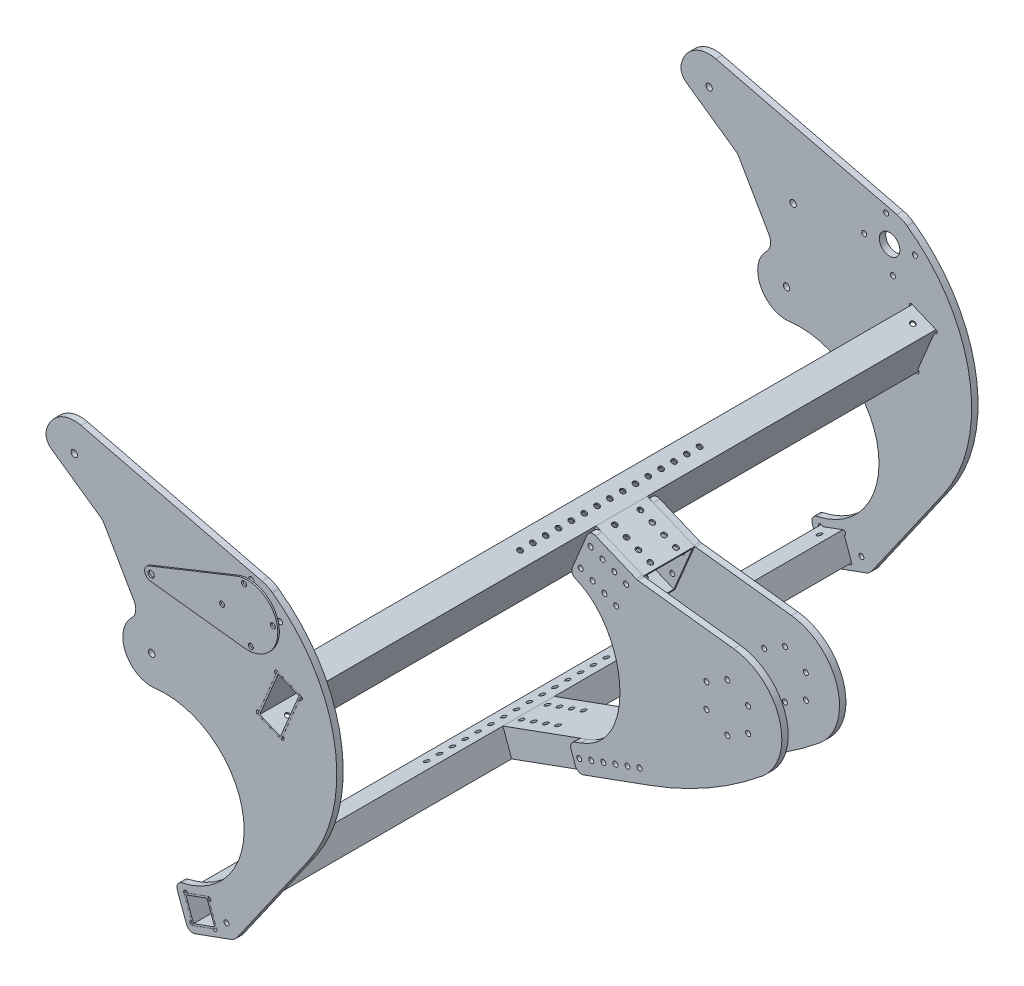
SolidWorks part; units mm, degrees
ref_plane "Front Plane" through (0, 0, 0) normal (0, 0, 1) x (1, 0, 0)
ref_plane "Top Plane" through (0, 0, 0) normal (0, 1, 0) x (1, 0, 0)
ref_plane "Right Plane" through (0, 0, 0) normal (1, 0, 0) x (0, 0, -1)
sketch "citrus are on lsd" plane through (0, 0, 0) normal (0, 0, 1) x (1, 0, 0)
  line L0 (-284.2463, 47.3015) -> (-284.2463, 72.7015) construction
  line L1 (-284.2463, 47.3015) -> (-277.7091, 122.0222) construction
  line L2 (-360.9349, 180.2976) -> (-277.7091, 122.0222) construction
  line L3 (-284.2463, 47.3015) -> (-309.6463, 47.3015) construction
  line L4 (-252.4225, -141.9521) -> (-228.5543, -133.2647)
  line L5 (0, 0) -> (50.8, 0) construction
  line L6 (-252.4225, -141.9521) -> (-243.7352, -165.8203)
  line L7 (-243.7352, -165.8203) -> (-219.867, -157.1329)
  line L8 (-219.867, -157.1329) -> (-228.5543, -133.2647)
  line L9 (-179.3681, 47.4325) -> (-155.9323, 37.6382)
  line L10 (-179.3681, 47.4325) -> (-159.7796, 94.3039)
  line L11 (-155.9323, 37.6382) -> (-136.3439, 84.5097)
  line L12 (-159.7796, 94.3039) -> (-136.3439, 84.5097)
  line L13 (-169.5738, 70.8682) -> (0, 0) construction
  line L14 (-136.3439, 84.5097) -> (-155.9323, 37.6382)
  line L15 (-136.3439, 84.5097) -> (-89.4724, 64.9212)
  line L16 (-155.9323, 37.6382) -> (-109.0609, 18.0498)
  line L17 (-89.4724, 64.9212) -> (-109.0609, 18.0498)
  line L18 (-228.5543, -133.2647) -> (-219.867, -157.1329)
  line L19 (-228.5543, -133.2647) -> (-85.3451, -81.1409)
  line L20 (-219.867, -157.1329) -> (-76.6578, -105.0091)
  line L21 (-85.3451, -81.1409) -> (-76.6578, -105.0091)
  circle A0 centre (0, 0) radius 50.3428 construction
  circle A2 centre (-284.2463, 47.3015) radius 25.4
  circle A3 centre (-277.7091, 122.0222) radius 25.4
  circle A4 centre (-360.9349, 180.2976) radius 25.4
  circle A5 centre (-236.1447, -149.5425) radius 12.7
  circle A6 centre (-182.2333, 134.7222) radius 30
  circle A7 centre (-182.2333, 134.7222) radius 11.5 construction
  circle A8 centre (-277.7091, 122.0222) radius 25.5 construction
  dimension "D4" = 50.8
  dimension "D3" = 75.0062
  dimension "D5" = 5
  dimension "D6" = 35
  dimension "D7" = 101.6
  dimension "D8" = 20
  dimension "D9" = 188.7245
  dimension "D10" = 25.4
  dimension "D11" = 260.35
  dimension "D12" = 149.5425
  dimension "D14" = 50.8
  dimension "D15" = 25.4
  dimension "D16" = 183.7868
  dimension "D17" = 22.681
  dimension "D19" = 96.3168
  dimension "D22" = 12.7
  dimension "D13" = 284.2463
  dimension "D23" = 152.4
  dimension "D24" = 50.8
sketch "rudimentary topdown" plane through (0, 0, 0) normal (0, 1, 0) x (1, 0, 0)
  line L0 (0, 330.2) -> (0, -330.2) construction
  line L1 (0, -31.75) -> (-179.3681, -31.75) construction
  line L2 (0, 25.4) -> (-179.3681, 25.4)
  line L3 (0, 25.4) -> (0, -25.4)
  line L4 (0, -25.4) -> (-179.3681, -25.4)
  line L5 (-179.3681, 25.4) -> (-179.3681, -25.4)
  line L6 (0, 0) -> (-481.5631, 0) construction
  line L7 (0, -317.5) -> (-386.3349, -317.5) construction
  line L8 (0, 31.75) -> (-179.3681, 31.75) construction
  line L9 (0, 311.15) -> (-386.3349, 311.15) construction
  line L10 (0, -311.15) -> (-386.3349, -311.15) construction
  line L11 (0, 317.5) -> (-386.3349, 317.5) construction
  line L12 (-360.9349, 317.5) -> (-360.9349, -317.5) construction
  line L13 (-277.7091, 317.5) -> (-277.7091, -317.5) construction
  line L14 (-284.2463, 317.5) -> (-284.2463, -317.5) construction
  line L15 (-179.3681, 317.5) -> (-179.3681, -317.5)
  line L16 (-386.3349, 317.5) -> (-335.5349, 317.5)
  line L17 (-386.3349, 317.5) -> (-386.3349, -317.5)
  line L18 (-386.3349, -317.5) -> (-335.5349, -317.5)
  line L19 (-335.5349, 317.5) -> (-335.5349, -317.5)
  line L20 (-309.6463, 317.5) -> (-252.3091, 317.5)
  line L21 (-309.6463, 317.5) -> (-309.6463, -317.5)
  line L22 (-309.6463, -317.5) -> (-252.3091, -317.5)
  line L23 (-252.3091, 317.5) -> (-252.3091, -317.5)
  line L24 (-136.3439, -317.5) -> (-136.3439, 317.5)
  line L25 (0, -330.2) -> (-386.3349, -330.2)
  line L26 (-252.4225, 317.5) -> (-219.867, 317.5)
  line L27 (-252.4225, 317.5) -> (-252.4225, -317.5)
  line L28 (-252.4225, -317.5) -> (-219.867, -317.5)
  line L29 (-219.867, 317.5) -> (-219.867, -317.5)
  line L31 (0, 330.2) -> (-386.3349, 330.2)
  point P4 (0, 0)
  point P11 (0, 0)
  dimension "D1" = 660.4
  dimension "D2" = 50.8
  dimension "D4" = 6.35
  dimension "D5" = 6.35
  dimension "D6" = 311.15
  dimension "D8" = 50.8
  dimension "D9" = 25.4
  dimension "D10" = 25.4
  dimension "D11" = 25.4
ref_plane "attachplateplane" through (0, 0, 25.4) normal (0, 0, 1) x (1, 0, 0)
ref_plane "intakeplateplane" through (0, 0, 311.15) normal (0, 0, 1) x (1, 0, 0)
sketch "intakeplate" plane through (0, 0, 311.15) normal (0, 0, 1) x (1, 0, 0)
  line L0 (-354.2108, 207.7434) -> (-175.0945, 163.8605)
  line L1 (-199.728, -154.1663) -> (-128.4497, -52.2564)
  line L3 (-360.9349, 180.2976) -> (-236.1447, -149.5425) construction
  line L4 (-255.0764, -134.809) -> (-243.3357, -130.5357) construction
  line L5 (-252.4225, -141.9521) -> (-228.5543, -133.2647) construction
  line L6 (-383.4957, 172.839) -> (-334.9996, 138.8818)
  line L7 (-331.2821, 134.8225) -> (-301.7087, 83.5353)
  line L8 (-137.8969, 80.6618) -> (-136.2774, 84.537) construction
  line L15 (-241.5937, -171.8524) -> (-205.7914, -158.8214)
  line L16 (-258.8716, -142.9479) -> (-249.7326, -168.0572)
  line L17 (-159.8069, 94.3704) -> (-161.4264, 90.4952) construction
  line L18 (-360.9349, 180.2976) -> (-277.7091, 122.0222) construction
  line L19 (-360.9349, 180.2976) -> (-284.2463, 47.3015) construction
  line L30 (-185.5824, 159.9005) -> (-182.2333, 134.7222) construction
  line L31 (-277.7091, 122.0222) -> (-182.2333, 134.7222) construction
  line L40 (-136.2774, 84.537) -> (-159.8069, 94.3704)
  line L41 (-159.8069, 94.3704) -> (-179.4345, 47.4052)
  line L42 (-179.4345, 47.4052) -> (-155.9051, 37.5718)
  line L43 (-155.9051, 37.5718) -> (-136.2774, 84.537)
  line L44 (-136.2774, 84.537) -> (-159.8069, 94.3704)
  line L45 (-161.4264, 90.4952) -> (-177.815, 51.2804)
  line L46 (-179.4345, 47.4052) -> (-155.9051, 37.5718)
  line L47 (-154.2855, 41.447) -> (-137.8969, 80.6618)
  line L48 (-227.0874, -137.1463) -> (-228.5239, -133.1996) construction
  line L49 (-223.7486, -158.5998) -> (-219.8019, -157.1633) construction
  line L50 (-245.202, -161.9387) -> (-243.7655, -165.8854) construction
  line L51 (-248.5409, -140.4852) -> (-252.4876, -141.9217) construction
  line L52 (-252.4876, -141.9217) -> (-243.7655, -165.8854)
  line L53 (-243.7655, -165.8854) -> (-219.8019, -157.1633)
  line L54 (-228.5239, -133.1996) -> (-252.4876, -141.9217)
  line L55 (-219.8019, -157.1633) -> (-228.5239, -133.1996)
  line L56 (-252.4876, -141.9217) -> (-245.202, -161.9387)
  line L57 (-243.7655, -165.8854) -> (-223.7486, -158.5998)
  line L58 (-228.5239, -133.1996) -> (-248.5409, -140.4852)
  line L59 (-219.8019, -157.1633) -> (-227.0874, -137.1463)
  line L60 (-155.9323, 37.6382) -> (-136.3439, 84.5097) construction
  line L61 (-155.9051, 37.5718) -> (-154.2855, 41.447) construction
  line L62 (-177.815, 51.2804) -> (-179.4345, 47.4052) construction
  arc A0 (-354.2108, 207.7434) -> (-388.6817, 185.6461) centre (-360.9349, 180.2976) ccw
  arc A2 (-303.9524, 67.9945) -> (-280.5976, 18.9604) centre (-284.2463, 47.3015) ccw
  circle A3 centre (-284.2463, 47.3015) radius 3.1877
  circle A4 centre (-277.7091, 122.0222) radius 3.1877
  circle A5 centre (-360.9349, 180.2976) radius 3.1877
  arc A6 (-241.5937, -171.8524) -> (-249.7326, -168.0572) centre (-243.7655, -165.8854) cw
  arc A9 (-164.8065, 159.1417) -> (-175.0945, 163.8605) centre (-182.2333, 134.7222) ccw
  arc A10 (-164.8065, 159.1417) -> (-128.4497, -52.2564) centre (-253.3344, 35.091) cw
  circle A11 centre (-182.2333, 134.7222) radius 30 construction
  arc A12 (-199.728, -154.1663) -> (-205.7914, -158.8214) centre (-210.1351, -146.8873) cw
  arc A14 (-254.2407, -134.5682) -> (-258.8716, -142.9479) centre (-252.9046, -140.776) ccw
  arc A15 (-284.2463, 47.3015) -> (-236.1447, -149.5425) centre (-272.2654, -54.07) cw construction
  arc A18 (-301.7087, 83.5353) -> (-303.9524, 67.9945) centre (-312.7107, 77.1913) cw
  arc A19 (-334.9996, 138.8818) -> (-331.2821, 134.8225) centre (-342.2841, 128.4785) cw
  arc A20 (-383.4957, 172.839) -> (-388.6817, 185.6461) centre (-376.2112, 183.2423) cw
  arc A21 (-280.5976, 18.9604) -> (-254.2407, -134.5682) centre (-270.6433, -58.3574) cw
  circle A25 centre (-182.2333, 134.7222) radius 25.4 construction
  circle A26 centre (-185.5824, 159.9005) radius 2.4892
  circle A27 centre (-157.055, 138.0714) radius 2.4892
  circle A28 centre (-178.8841, 109.544) radius 2.4892
  circle A29 centre (-207.4115, 131.3731) radius 2.4892
  arc A30 (-228.5239, -133.1996) -> (-227.0874, -137.1463) centre (-227.8057, -135.173) cw
  arc A31 (-219.8019, -157.1633) -> (-223.7486, -158.5998) centre (-221.7752, -157.8815) cw
  arc A32 (-243.7655, -165.8854) -> (-245.202, -161.9387) centre (-244.4838, -163.912) cw
  arc A33 (-252.4876, -141.9217) -> (-248.5409, -140.4852) centre (-250.5142, -141.2035) cw
  arc A34 (-155.9051, 37.5718) -> (-154.2855, 41.447) centre (-155.0953, 39.5094) ccw
  arc A35 (-159.8069, 94.3704) -> (-161.4264, 90.4952) centre (-160.6166, 92.4328) ccw
  arc A36 (-136.2774, 84.537) -> (-137.9436, 80.6819) centre (-137.0872, 82.5994) cw
  arc A37 (-179.4345, 47.4052) -> (-177.815, 51.2804) centre (-178.6248, 49.3428) cw
  circle A38 centre (-182.2333, 134.7222) radius 10.16
  circle A39 centre (-210.1351, -146.8873) radius 2.4892
  point P64 (-182.2333, 134.7222)
  point P83 (-236.1447, -149.5425)
  dimension "D2" = 6.35
  dimension "D4" = 152.4
  dimension "D5" = 6.3754
  dimension "D6" = 56.515
  dimension "D7" = 57.15
  dimension "D8" = 102.077
  dimension "D13" = 12.7
  dimension "D11" = 50.8
  dimension "D15" = 4.9784
  dimension "D18" = 2.1
  dimension "D20" = 2.1
  dimension "D23" = 20.32
  dimension "D24" = 4.9784
  dimension "D3" = 127
  dimension "D9" = 7.62
  dimension "D10" = 38.1
  dimension "D12" = 19.05
  dimension "D21" = 6.35
  dimension "D22" = 6.35
  dimension "D14" = 4
sketch "attachplate" plane through (0, 0, 25.4) normal (0, 0, 1) x (1, 0, 0)
  line L0 (-136.3439, 84.5097) -> (-155.9323, 37.6382)
  line L1 (-136.3439, 84.5097) -> (-89.4724, 64.9212)
  line L2 (-155.9323, 37.6382) -> (-109.0609, 18.0498)
  line L3 (-89.4724, 64.9212) -> (-109.0609, 18.0498) construction
  line L4 (-228.5543, -133.2647) -> (-219.867, -157.1329) construction
  line L5 (-156.9497, -107.2028) -> (-85.3451, -81.1409)
  line L6 (-148.2624, -131.071) -> (-76.6578, -105.0091)
  line L7 (-85.3451, -81.1409) -> (-76.6578, -105.0091) construction
  line L8 (-81.0015, -93.075) -> (-152.606, -119.1369) construction
  line L9 (6.3329, 53.6022) -> (-89.4724, 64.9212)
  line L10 (-156.9497, -107.2028) -> (-148.2624, -131.071)
  line L11 (-219.867, -157.1329) -> (-148.2624, -131.071) construction
  line L12 (-228.5543, -133.2647) -> (-156.9497, -107.2028) construction
  line L14 (-169.5738, 70.8682) -> (0, 0) construction
  line L15 (-169.5738, 70.8682) -> (0, 0) construction
  line L16 (-85.3451, -81.1409) -> (-123.6697, 24.1551) construction
  arc A0 (34.2825, -41.6895) -> (6.3329, 53.6022) centre (0, 0) ccw
  circle A1 centre (0, 23.8125) radius 2.4892
  circle A2 centre (20.6222, 11.9063) radius 2.4892
  circle A3 centre (20.6222, -11.9062) radius 2.4892
  circle A4 centre (0, -23.8125) radius 2.4892
  circle A5 centre (-20.6222, -11.9063) radius 2.4892
  circle A6 centre (-20.6222, 11.9062) radius 2.4892
  circle A7 centre (0, 0) radius 23.8125 construction
  arc A9 (-76.6578, -105.0091) -> (34.2825, -41.6895) centre (-206.0995, 250.6289) ccw
  circle A10 centre (-100.2285, 55.6519) radius 2.4892
  circle A11 centre (-111.9463, 60.549) radius 2.4892
  arc A12 (6.3329, 53.6022) -> (34.2825, -41.6895) centre (0, 0) ccw construction
  circle A13 centre (-86.9685, -95.2468) radius 2.4892
  circle A14 centre (-98.9026, -99.5905) radius 2.4892
  circle A15 centre (-110.8367, -103.9341) radius 2.4892
  circle A16 centre (-122.7708, -108.2778) radius 2.4892
  circle A17 centre (-134.7049, -112.6214) radius 2.4892
  circle A18 centre (-123.6642, 65.4461) radius 2.4892
  circle A19 centre (-135.382, 70.3433) radius 2.4892
  circle A20 centre (-146.639, -116.9651) radius 2.4892
  circle A21 centre (-145.1763, 46.9075) radius 2.4892
  circle A22 centre (-133.4584, 42.0104) radius 2.4892
  circle A23 centre (-121.7406, 37.1133) radius 2.4892
  circle A24 centre (-110.0227, 32.2162) radius 2.4892
  spline S0 degree 3 poles (-145.0156, -102.8592) (-86.7961, -81.669) (-99.0931, 15.0965) (-150.0777, 35.1793) knots 0 0 0 0 1 1 1 1
  point P29 (0, 0)
  dimension "D1" = 107.95
  dimension "D4" = 4.9784
  dimension "D6" = 47.625
  dimension "D10" = 4.9784
  dimension "D18" = 4.9784
  dimension "D2" = 50.8
  dimension "D3" = 152.4
  dimension "D7" = 76.2
  dimension "D9" = 6.35
  dimension "D11" = 12.7
  dimension "D12" = 12.7
  dimension "D13" = 6.35
  dimension "D14" = 109.4363
  dimension "D15" = 138.1559
  dimension "D16" = 12.7
  dimension "D17" = 6.35
  dimension "D20" = 12.7
  dimension "D8" = 6
  dimension "D19" = 4
  dimension "D5" = 6
ref_plane "motorstiffplane" through (0, 0, 323.85) normal (0, 0, 1) x (1, 0, 0)
sketch "motorplate" plane through (0, 0, 323.85) normal (0, 0, 1) x (1, 0, 0)
  line L0 (-280.0663, 127.9185) -> (-193.3699, 162.5786)
  line L1 (-185.7007, 104.9233) -> (-278.443, 115.7148)
  circle A0 centre (-277.7091, 122.0222) radius 3.1877 construction
  circle A1 centre (-207.4115, 131.3731) radius 2.4892 construction
  circle A2 centre (-178.8841, 109.544) radius 2.4892 construction
  circle A3 centre (-157.055, 138.0714) radius 2.4892 construction
  circle A4 centre (-185.5824, 159.9005) radius 2.4892 construction
  circle A5 centre (-277.7091, 122.0222) radius 3.1877
  circle A6 centre (-207.4115, 131.3731) radius 2.4892
  circle A7 centre (-178.8841, 109.544) radius 2.4892
  circle A8 centre (-157.055, 138.0714) radius 2.4892
  circle A9 centre (-185.5824, 159.9005) radius 2.4892
  arc A10 (-185.7007, 104.9233) -> (-193.3699, 162.5786) centre (-182.2333, 134.7222) ccw
  arc A11 (-280.0663, 127.9185) -> (-278.443, 115.7148) centre (-277.7091, 122.0222) ccw
  arc A12 (-278.443, 115.7148) -> (-280.0663, 127.9185) centre (-277.7091, 122.0222) ccw construction
  arc A13 (-193.3699, 162.5786) -> (-185.7007, 104.9233) centre (-182.2333, 134.7222) ccw construction
  circle A14 centre (-182.2333, 134.7222) radius 30 construction
  dimension "D1" = 6.35
extrude "intake plate" add sketch "intakeplate" along normal blind 6.35 contours A2 A21 A14 L16 A6 L15 A12 L1 A10 A9 L0 A0 A20 L6 A19 L7 A18 A38 A29 A28 A27 A26 A3 A4 A5 L56 A33 L58 A30 L59 A31 L57 A32 L46 A37 L45 A35 L44 A36 L47 A34 region at (-219.5502, 62.0927, 311.15)
extrude "attach plate" add sketch "attachplate" along normal blind 6.35 separate body contours S0 L5 L10 L6 A9 A0 L9 L1 L0 L2 A23 A21 A20 A19 A18 A17 A16 A15 A14 A13 A11 A10 A6 A5 A4 A3 A2 A1 region at (-53.0442, -13.4193, 25.4)
fillet "Fillet1" radius 6.35 5 edges at (-155.9323, 37.6382, 28.575) (-136.3439, 84.5097, 28.575) (-89.4724, 64.9212, 28.575) (-148.2624, -131.071, 28.575) (-156.9497, -107.2028, 28.575)
mirror "Mirror1" about plane through (0, 0, 0) normal (0, 0, 1) of bodies 101 102
extrude "tubes" add sketch "citrus are on lsd" along normal mid plane 635 separate body contours L12 L11 L9 L10 | L7 L8 L4 L6
shell "Shell1" thickness 1.5875 removed face at (-157.856, 65.9711, -317.5) removed face at (-157.856, 65.9711, 317.5)
shell "Shell2" thickness 1.5875 removed face at (-236.1447, -149.5425, -317.5) removed face at (-236.1447, -149.5425, 317.5)
extrude "motor plate" add sketch "motorplate" along normal mid plane 1.5875 separate body
extrude "Boss-Extrude5" add sketch "citrus are on lsd<3>" along normal mid plane 50.8 separate body contours L17 L15 L11 L16 | L21 L19 L18 L8 L20 region at (-152.606, -119.1369, 0) region at (-122.7024, 51.2797, 0)
sketch "citrus are on lsd<3>" plane through (0, 0, 0) normal (0, 0, 1) x (1, 0, 0) same geometry as "citrus are on lsd"
shell "Shell3" thickness 1.5875 removed face at (-146.1381, 61.074, 0) removed face at (-99.2667, 41.4855, 0)
shell "Shell4" thickness 1.5875 removed face at (-81.0015, -93.075, 0) removed face at (-224.2106, -145.1988, 0)
sketch "Sketch2" plane through (0, 0, 25.4) normal (0, 0, 1) x (1, 0, 0)
  circle A0 centre (-134.7049, -112.6214) radius 2.4892 construction
  circle A1 centre (-146.639, -116.9651) radius 2.4892 construction
  circle A2 centre (-122.7708, -108.2778) radius 2.4892 construction
  circle A3 centre (-110.8367, -103.9341) radius 2.4892 construction
  circle A4 centre (-98.9026, -99.5905) radius 2.4892 construction
  circle A5 centre (-86.9685, -95.2468) radius 2.4892 construction
  circle A6 centre (-134.7049, -112.6214) radius 2.4892
  circle A7 centre (-146.639, -116.9651) radius 2.4892
  circle A8 centre (-122.7708, -108.2778) radius 2.4892
  circle A9 centre (-110.8367, -103.9341) radius 2.4892
  circle A10 centre (-98.9026, -99.5905) radius 2.4892
  circle A11 centre (-86.9685, -95.2468) radius 2.4892
  circle A12 centre (-145.1763, 46.9075) radius 2.4892 construction
  circle A13 centre (-133.4584, 42.0104) radius 2.4892 construction
  circle A14 centre (-110.0227, 32.2162) radius 2.4892 construction
  circle A15 centre (-121.7406, 37.1133) radius 2.4892 construction
  circle A16 centre (-100.2285, 55.6519) radius 2.4892 construction
  circle A17 centre (-111.9463, 60.549) radius 2.4892 construction
  circle A18 centre (-123.6642, 65.4461) radius 2.4892 construction
  circle A19 centre (-135.382, 70.3433) radius 2.4892 construction
  circle A20 centre (-145.1763, 46.9075) radius 2.4892
  circle A21 centre (-133.4584, 42.0104) radius 2.4892
  circle A22 centre (-110.0227, 32.2162) radius 2.4892
  circle A23 centre (-121.7406, 37.1133) radius 2.4892
  circle A24 centre (-100.2285, 55.6519) radius 2.4892
  circle A25 centre (-111.9463, 60.549) radius 2.4892
  circle A26 centre (-123.6642, 65.4461) radius 2.4892
  circle A27 centre (-135.382, 70.3433) radius 2.4892
extrude "Cut-Extrude1" cut sketch "Sketch2" against normal through all
sketch "Sketch3" plane through (9.7942, 23.4357, 0) normal (0.3856, 0.9227, 0) x (0.9227, -0.3856, 0)
  line L0 (-171.0868, -317.5) -> (-171.0868, 317.5) construction
  line L1 (-183.7868, -317.5) -> (-158.3868, -317.5) construction
  line L2 (-183.7868, 317.5) -> (-158.3868, 317.5) construction
  line L3 (-107.5868, -12.7) -> (-158.3868, -12.7) construction
  line L4 (-107.5868, -25.4) -> (-107.5868, 25.4) construction
  line L5 (-158.3868, -25.4) -> (-158.3868, 25.4) construction
  line L6 (-107.5868, 12.7) -> (-158.3868, 12.7) construction
  line L7 (-158.3868, -25.4) -> (-107.5868, -25.4) construction
  line L8 (-158.3868, 25.4) -> (-107.5868, 25.4) construction
  circle A0 centre (-152.0368, -12.7) radius 2.4892
  circle A1 centre (-152.0368, 12.7) radius 2.4892
  circle A2 centre (-171.0868, -88.9) radius 2.4892
  circle A3 centre (-171.0868, -76.2) radius 2.4892
  circle A4 centre (-171.0868, -63.5) radius 2.4892
  circle A5 centre (-171.0868, -50.8) radius 2.4892
  circle A6 centre (-171.0868, -38.1) radius 2.4892
  circle A7 centre (-171.0868, -25.4) radius 2.4892
  circle A8 centre (-171.0868, -12.7) radius 2.4892
  circle A9 centre (-171.0868, 0) radius 2.4892
  circle A10 centre (-171.0868, 12.7) radius 2.4892
  circle A11 centre (-171.0868, 25.4) radius 2.4892
  circle A12 centre (-171.0868, 38.1) radius 2.4892
  circle A13 centre (-171.0868, 50.8) radius 2.4892
  circle A14 centre (-139.3368, -12.7) radius 2.4892
  circle A15 centre (-139.3368, 12.7) radius 2.4892
  circle A16 centre (-126.6368, -12.7) radius 2.4892
  circle A17 centre (-126.6368, 12.7) radius 2.4892
  circle A18 centre (-113.9368, -12.7) radius 2.4892
  circle A19 centre (-113.9368, 12.7) radius 2.4892
  circle A20 centre (-171.0868, 63.5) radius 2.4892
  circle A21 centre (-171.0868, 76.2) radius 2.4892
  circle A22 centre (-171.0868, 88.9) radius 2.4892
  circle A23 centre (-171.0868, -300.0375) radius 2.4892
  circle A24 centre (-171.0868, 300.0375) radius 2.4892
  point P25 (-171.0868, 0)
  dimension "D3" = 4.9784
  dimension "D11" = 17.4625
  dimension "D1" = 12.7
  dimension "D2" = 12.7
  dimension "D4" = 88.9
  dimension "D5" = 6.35
  dimension "D7" = 12.7
  dimension "D9" = 12.7
  dimension "D10" = 17.4625
  dimension "D6" = 15
  dimension "D8" = 4
extrude "Cut-Extrude2" cut sketch "Sketch3" against normal through all
sketch "Sketch7" plane through (16.0947, -44.2198, 0) normal (-0.342, 0.9397, 0) x (0.9397, 0.342, 0)
  line L0 (-273.05, 317.5) -> (-273.05, -317.5) construction
  line L1 (-285.75, 317.5) -> (-260.35, 317.5) construction
  line L2 (-285.75, -317.5) -> (-260.35, -317.5) construction
  line L3 (-107.95, -12.7) -> (-260.35, -12.7) construction
  line L4 (-107.95, 12.7) -> (-260.35, 12.7) construction
  line L5 (-55, 0) -> (55, 0) construction
  line L6 (-260.35, -25.4) -> (-260.35, 25.4) construction
  line L7 (-260.35, -317.5) -> (-260.35, 317.5) construction
  line L8 (-260.35, -25.4) -> (-107.95, -25.4) construction
  line L9 (-260.35, 25.4) -> (-107.95, 25.4) construction
  line L10 (-107.95, -25.4) -> (-107.95, 25.4) construction
  circle A0 centre (-254, -12.7) radius 2.4892
  circle A1 centre (-254, 12.7) radius 2.4892
  circle A2 centre (-273.05, -88.9) radius 2.4892
  circle A23 centre (-273.05, -76.2) radius 2.4892
  circle A24 centre (-273.05, -63.5) radius 2.4892
  circle A25 centre (-273.05, -50.8) radius 2.4892
  circle A26 centre (-273.05, -38.1) radius 2.4892
  circle A27 centre (-273.05, -25.4) radius 2.4892
  circle A28 centre (-273.05, -12.7) radius 2.4892
  circle A29 centre (-273.05, 0) radius 2.4892
  circle A30 centre (-273.05, 12.7) radius 2.4892
  circle A31 centre (-273.05, 25.4) radius 2.4892
  circle A32 centre (-273.05, 38.1) radius 2.4892
  circle A33 centre (-273.05, 50.8) radius 2.4892
  circle A34 centre (-273.05, 63.5) radius 2.4892
  circle A35 centre (-273.05, 76.2) radius 2.4892
  circle A36 centre (-273.05, 88.9) radius 2.4892
  circle A37 centre (-241.3, 12.7) radius 2.4892
  circle A38 centre (-241.3, -12.7) radius 2.4892
  circle A39 centre (-228.6, 12.7) radius 2.4892
  circle A40 centre (-228.6, -12.7) radius 2.4892
  circle A41 centre (-215.9, 12.7) radius 2.4892
  circle A42 centre (-215.9, -12.7) radius 2.4892
  circle A43 centre (-273.05, -300.0375) radius 2.4892
  circle A44 centre (-273.05, 300.0375) radius 2.4892
  dimension "D1" = 4.9784
  dimension "D2" = 88.9
  dimension "D3" = 12.7
  dimension "D4" = 12.7
  dimension "D5" = 6.35
  dimension "D7" = 12.7
  dimension "D9" = 12.7
  dimension "D10" = 17.4625
  dimension "D11" = 17.4625
  dimension "D6" = 15
  dimension "D8" = 4
extrude "Cut-Extrude3" cut sketch "Sketch7" against normal through all
equation "\"D18@citrus are on lsd\"=60mm"
equation "\"D20@citrus are on lsd\"=23mm"
equation "\"D21@citrus are on lsd\"=51MM"
equation "\"D18@intakeplate\"=2.1mm"
equation "\"D20@intakeplate\"=2.1mm"
